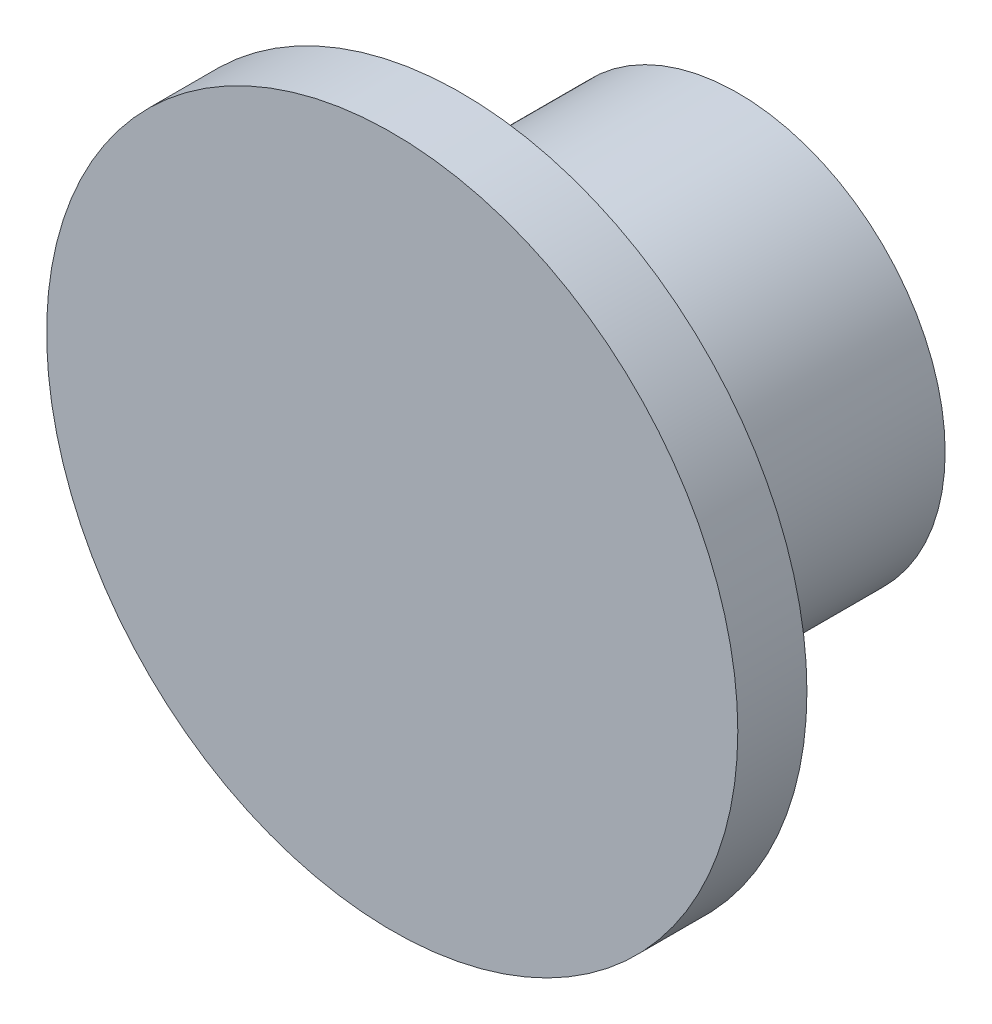
SolidWorks part; units mm, degrees
ref_plane "Front Plane" through (0, 0, 0) normal (0, 0, 1) x (1, 0, 0)
ref_plane "Top Plane" through (0, 0, 0) normal (0, 1, 0) x (1, 0, 0)
ref_plane "Right Plane" through (0, 0, 0) normal (1, 0, 0) x (0, 0, -1)
sketch "Sketch1" plane through (0, 0, 0) normal (0, 0, 1) x (1, 0, 0)
  circle A0 centre (0, 0) radius 25
  circle A1 centre (0, 0) radius 15
extrude "Boss-Extrude8" add sketch "Sketch1" along normal blind 5 contours A0 A1 | A1 region at (-24.2929, 0, 0)
extrude "Boss-Extrude9" add sketch "Sketch1<19>" against normal blind 20 contours A1 region at (0, 0, 0)
sketch "Sketch1<19>" plane through (0, 0, 0) normal (0, 0, 1) x (1, 0, 0) same geometry as "Sketch1"
